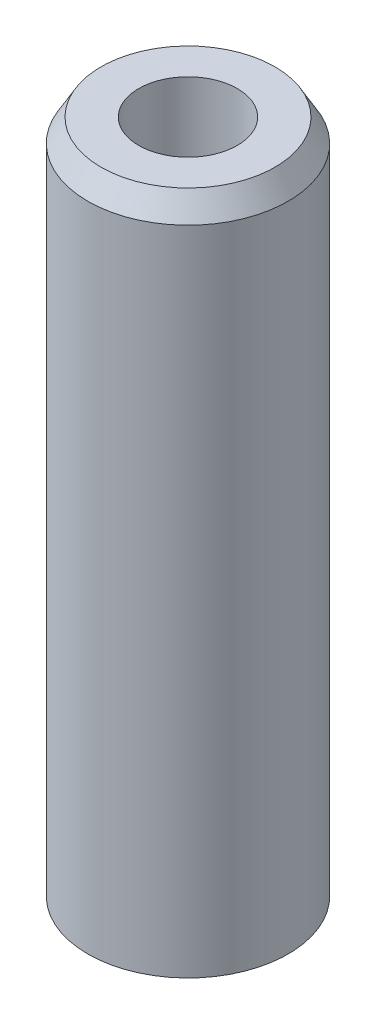
SolidWorks part; units mm, degrees
ref_plane "Front Plane" through (0, 0, 0) normal (0, 0, 1) x (1, 0, 0)
ref_plane "Top Plane" through (0, 0, 0) normal (0, 1, 0) x (1, 0, 0)
ref_plane "Right Plane" through (0, 0, 0) normal (1, 0, 0) x (0, 0, -1)
sketch "Sketch1" plane through (0, 0, 0) normal (0, 1, 0) x (1, 0, 0)
  circle A0 centre (0, 0) radius 15
  dimension "SHAFT_OD" = 30
extrude "Boss-Extrude1" add sketch "Sketch1" along normal blind 102.9948
sketch "Sketch2" plane through (0, 0, 0) normal (0, 1, 0) x (1, 0, 0)
  circle A0 centre (0, 0) radius 7.3805
  dimension "BORE_D" = 14.761
extrude "Cut-Extrude1" cut sketch "Sketch2" along normal through all
chamfer "Chamfer1" distance 3.4256 angle 30 2 edges at (0, 102.9948, 15) (0, 0, 15) first distance on face at (0, 102.9948, 15) first distance on face at (0, 0, 7.3805)
